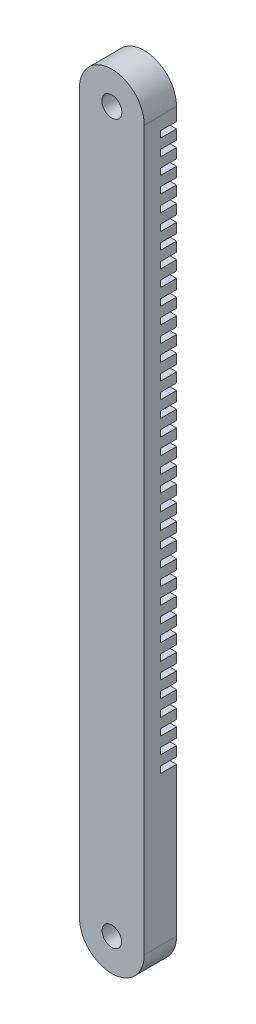
SolidWorks part; units mm, degrees
ref_plane "Front Plane" through (0, 0, 0) normal (0, 0, 1) x (1, 0, 0)
ref_plane "Top Plane" through (0, 0, 0) normal (0, 1, 0) x (1, 0, 0)
ref_plane "Right Plane" through (0, 0, 0) normal (1, 0, 0) x (0, 0, -1)
sketch "Sketch1" plane through (0, 0, 0) normal (0, 0, 1) x (1, 0, 0)
  line L0 (111, 0) -> (-111, 0) construction
  line L3 (0, 111) -> (0, -111) construction
  line L4 (0, 0) -> (0, -111) construction
  line L5 (5, 0) -> (5, -111)
  line L6 (-5, 0) -> (-5, -111)
  circle A2 centre (0, 0) radius 1.55
  circle A3 centre (0, -111) radius 1.5
  arc A4 (5, 0) -> (-5, 0) centre (0, 0) ccw
  arc A5 (-5, -111) -> (5, -111) centre (0, -111) ccw
  point P0 (0, -55.5)
  point P3 (0, 0)
  point P6 (6.9267, -114.2205)
  point P7 (51.3427, -127.4089)
  point P12 (0, 0)
  point P13 (0, 0)
  point P14 (0, 0)
  dimension "D1" = 5
  dimension "D2" = 111
  dimension "D3" = 3
  dimension "D4" = 3.1
extrude "Boss-Extrude1" add sketch "Sketch1" along normal blind 5
sketch "Sketch2" plane through (5, 0, 0) normal (1, 0, 0) x (0, 0, -1)
  line L143 (0, -111) -> (0, 0) construction
  line L144 (0, -2) -> (-2.5, -2)
  line L145 (0, -2) -> (0, -3)
  line L146 (0, -3) -> (-2.5, -3)
  line L147 (-2.5, -2) -> (-2.5, -3)
  line L148 (-5, 0) -> (0, 0) construction
  line L149 (0, -4.5) -> (0, -5.5)
  line L150 (0, -4.5) -> (-2.5, -4.5)
  line L151 (-2.5, -4.5) -> (-2.5, -5.5)
  line L152 (0, -5.5) -> (-2.5, -5.5)
  line L153 (0, -7) -> (0, -8)
  line L154 (0, -7) -> (-2.5, -7)
  line L155 (-2.5, -7) -> (-2.5, -8)
  line L156 (0, -8) -> (-2.5, -8)
  line L157 (0, -9.5) -> (0, -10.5)
  line L158 (0, -9.5) -> (-2.5, -9.5)
  line L159 (-2.5, -9.5) -> (-2.5, -10.5)
  line L160 (0, -10.5) -> (-2.5, -10.5)
  line L161 (0, -12) -> (0, -13)
  line L162 (0, -12) -> (-2.5, -12)
  line L163 (-2.5, -12) -> (-2.5, -13)
  line L164 (0, -13) -> (-2.5, -13)
  line L165 (0, -14.5) -> (0, -15.5)
  line L166 (0, -14.5) -> (-2.5, -14.5)
  line L167 (-2.5, -14.5) -> (-2.5, -15.5)
  line L168 (0, -15.5) -> (-2.5, -15.5)
  line L169 (0, -17) -> (0, -18)
  line L170 (0, -17) -> (-2.5, -17)
  line L171 (-2.5, -17) -> (-2.5, -18)
  line L172 (0, -18) -> (-2.5, -18)
  line L173 (0, -19.5) -> (0, -20.5)
  line L174 (0, -19.5) -> (-2.5, -19.5)
  line L175 (-2.5, -19.5) -> (-2.5, -20.5)
  line L176 (0, -20.5) -> (-2.5, -20.5)
  line L177 (0, -22) -> (0, -23)
  line L178 (0, -22) -> (-2.5, -22)
  line L179 (-2.5, -22) -> (-2.5, -23)
  line L180 (0, -23) -> (-2.5, -23)
  line L181 (0, -24.5) -> (0, -25.5)
  line L182 (0, -24.5) -> (-2.5, -24.5)
  line L183 (-2.5, -24.5) -> (-2.5, -25.5)
  line L184 (0, -25.5) -> (-2.5, -25.5)
  line L185 (0, -27) -> (0, -28)
  line L186 (0, -27) -> (-2.5, -27)
  line L187 (-2.5, -27) -> (-2.5, -28)
  line L188 (0, -28) -> (-2.5, -28)
  line L189 (0, -29.5) -> (0, -30.5)
  line L190 (0, -29.5) -> (-2.5, -29.5)
  line L191 (-2.5, -29.5) -> (-2.5, -30.5)
  line L192 (0, -30.5) -> (-2.5, -30.5)
  line L193 (0, -32) -> (0, -33)
  line L194 (0, -32) -> (-2.5, -32)
  line L195 (-2.5, -32) -> (-2.5, -33)
  line L196 (0, -33) -> (-2.5, -33)
  line L197 (0, -34.5) -> (0, -35.5)
  line L198 (0, -34.5) -> (-2.5, -34.5)
  line L199 (-2.5, -34.5) -> (-2.5, -35.5)
  line L200 (0, -35.5) -> (-2.5, -35.5)
  line L201 (0, -37) -> (0, -38)
  line L202 (0, -37) -> (-2.5, -37)
  line L203 (-2.5, -37) -> (-2.5, -38)
  line L204 (0, -38) -> (-2.5, -38)
  line L205 (0, -39.5) -> (0, -40.5)
  line L206 (0, -39.5) -> (-2.5, -39.5)
  line L207 (-2.5, -39.5) -> (-2.5, -40.5)
  line L208 (0, -40.5) -> (-2.5, -40.5)
  line L209 (0, -42) -> (0, -43)
  line L210 (0, -42) -> (-2.5, -42)
  line L211 (-2.5, -42) -> (-2.5, -43)
  line L212 (0, -43) -> (-2.5, -43)
  line L213 (0, -44.5) -> (0, -45.5)
  line L214 (0, -44.5) -> (-2.5, -44.5)
  line L215 (-2.5, -44.5) -> (-2.5, -45.5)
  line L216 (0, -45.5) -> (-2.5, -45.5)
  line L217 (0, -47) -> (0, -48)
  line L218 (0, -47) -> (-2.5, -47)
  line L219 (-2.5, -47) -> (-2.5, -48)
  line L220 (0, -48) -> (-2.5, -48)
  line L221 (0, -49.5) -> (0, -50.5)
  line L222 (0, -49.5) -> (-2.5, -49.5)
  line L223 (-2.5, -49.5) -> (-2.5, -50.5)
  line L224 (0, -50.5) -> (-2.5, -50.5)
  line L225 (0, -52) -> (0, -53)
  line L226 (0, -52) -> (-2.5, -52)
  line L227 (-2.5, -52) -> (-2.5, -53)
  line L228 (0, -53) -> (-2.5, -53)
  line L229 (0, -54.5) -> (0, -55.5)
  line L230 (0, -54.5) -> (-2.5, -54.5)
  line L231 (-2.5, -54.5) -> (-2.5, -55.5)
  line L232 (0, -55.5) -> (-2.5, -55.5)
  line L233 (0, -57) -> (0, -58)
  line L234 (0, -57) -> (-2.5, -57)
  line L235 (-2.5, -57) -> (-2.5, -58)
  line L236 (0, -58) -> (-2.5, -58)
  line L237 (0, -59.5) -> (0, -60.5)
  line L238 (0, -59.5) -> (-2.5, -59.5)
  line L239 (-2.5, -59.5) -> (-2.5, -60.5)
  line L240 (0, -60.5) -> (-2.5, -60.5)
  line L241 (0, -62) -> (0, -63)
  line L242 (0, -62) -> (-2.5, -62)
  line L243 (-2.5, -62) -> (-2.5, -63)
  line L244 (0, -63) -> (-2.5, -63)
  line L245 (0, -64.5) -> (0, -65.5)
  line L246 (0, -64.5) -> (-2.5, -64.5)
  line L247 (-2.5, -64.5) -> (-2.5, -65.5)
  line L248 (0, -65.5) -> (-2.5, -65.5)
  line L249 (0, -67) -> (0, -68)
  line L250 (0, -67) -> (-2.5, -67)
  line L251 (-2.5, -67) -> (-2.5, -68)
  line L252 (0, -68) -> (-2.5, -68)
  line L253 (0, -69.5) -> (0, -70.5)
  line L254 (0, -69.5) -> (-2.5, -69.5)
  line L255 (-2.5, -69.5) -> (-2.5, -70.5)
  line L256 (0, -70.5) -> (-2.5, -70.5)
  line L257 (0, -72) -> (0, -73)
  line L258 (0, -72) -> (-2.5, -72)
  line L259 (-2.5, -72) -> (-2.5, -73)
  line L260 (0, -73) -> (-2.5, -73)
  line L261 (0, -74.5) -> (0, -75.5)
  line L262 (0, -74.5) -> (-2.5, -74.5)
  line L263 (-2.5, -74.5) -> (-2.5, -75.5)
  line L264 (0, -75.5) -> (-2.5, -75.5)
  line L265 (0, -77) -> (0, -78)
  line L266 (0, -77) -> (-2.5, -77)
  line L267 (-2.5, -77) -> (-2.5, -78)
  line L268 (0, -78) -> (-2.5, -78)
  line L269 (0, -79.5) -> (0, -80.5)
  line L270 (0, -79.5) -> (-2.5, -79.5)
  line L271 (-2.5, -79.5) -> (-2.5, -80.5)
  line L272 (0, -80.5) -> (-2.5, -80.5)
  line L273 (0, -82) -> (0, -83)
  line L274 (0, -82) -> (-2.5, -82)
  line L275 (-2.5, -82) -> (-2.5, -83)
  line L276 (0, -83) -> (-2.5, -83)
  line L277 (0, -84.5) -> (0, -85.5)
  line L278 (0, -84.5) -> (-2.5, -84.5)
  line L279 (-2.5, -84.5) -> (-2.5, -85.5)
  line L280 (0, -85.5) -> (-2.5, -85.5)
  line L281 (0, -87) -> (0, -88)
  line L282 (0, -87) -> (-2.5, -87)
  line L283 (-2.5, -87) -> (-2.5, -88)
  line L284 (0, -88) -> (-2.5, -88)
  dimension "D1" = 2.5
  dimension "D2" = 1
  dimension "D3" = 2
  dimension "D4" = 35
extrude "Cut-Extrude1" cut sketch "Sketch2" against normal through all
